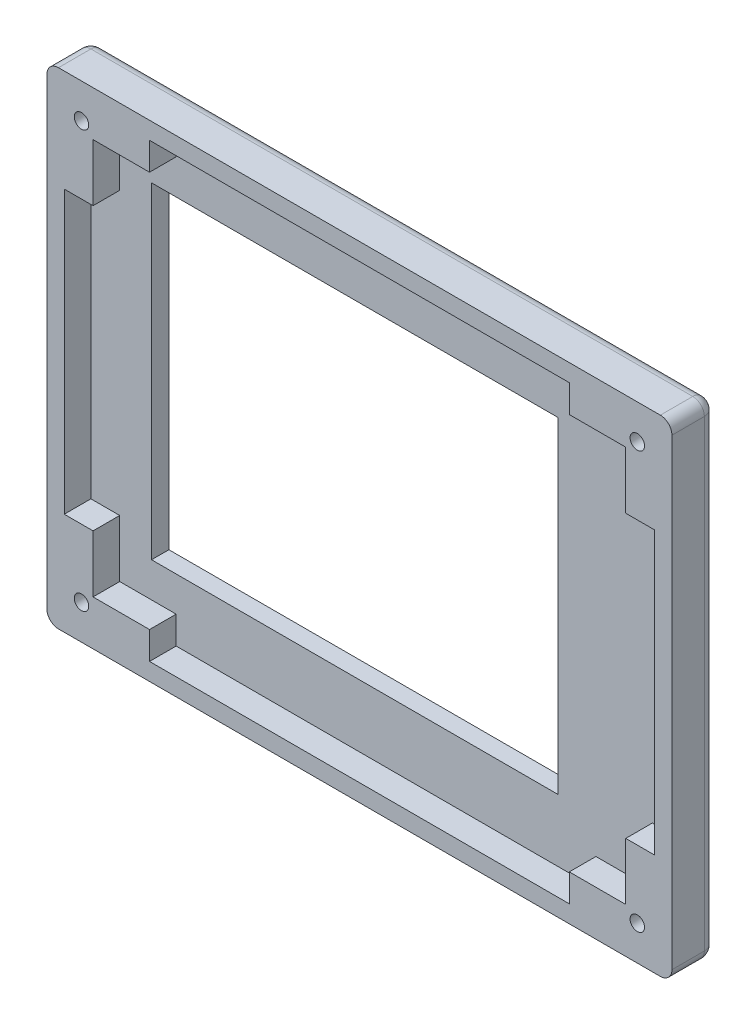
SolidWorks part; units mm, degrees
ref_plane "前视基准面" through (0, 0, 0) normal (0, 0, 1) x (1, 0, 0)
ref_plane "上视基准面" through (0, 0, 0) normal (0, 1, 0) x (1, 0, 0)
ref_plane "右视基准面" through (0, 0, 0) normal (1, 0, 0) x (0, 0, -1)
other "Configuration Table"
sketch "草图1" plane through (0, 0, 0) normal (0, 0, 1) x (1, 0, 0)
  line L32 (0.7633, 42.7757) -> (0.7633, 44.263) construction
  line L33 (0.7633, 44.263) -> (-41.2112, 44.263) construction
  line L34 (-41.2112, 44.263) -> (-41.2112, 42.7757) construction
  line L35 (-44.2239, 39.763) -> (-45.7112, 39.763) construction
  line L36 (-45.7112, 39.763) -> (-45.7112, 9.7885) construction
  line L37 (-45.7112, 9.7885) -> (-44.2239, 9.7885) construction
  line L38 (-41.2112, 6.7758) -> (-41.2112, 5.2885) construction
  line L39 (-41.2112, 5.2885) -> (0.7633, 5.2885) construction
  line L40 (0.7633, 5.2885) -> (0.7633, 6.7758) construction
  line L41 (3.776, 9.7885) -> (5.2633, 9.7885) construction
  line L42 (5.2633, 9.7885) -> (5.2633, 20.2756) construction
  line L43 (5.2633, 20.2756) -> (-0.4009, 20.283) construction
  line L44 (-0.4136, 20.2957) -> (-0.4136, 29.2557) construction
  line L45 (-0.4009, 29.2684) -> (5.2633, 29.2684) construction
  line L46 (5.2633, 29.2684) -> (5.2633, 39.763) construction
  line L47 (5.2633, 39.763) -> (3.776, 39.763) construction
  circle A1 centre (-4.0239, 32.2757) radius 1.125 construction
  arc A12 (0.7633, 42.7757) -> (3.776, 39.763) centre (3.776, 42.7757) ccw construction
  arc A13 (-44.2239, 39.763) -> (-41.2112, 42.7757) centre (-44.2239, 42.7757) ccw construction
  arc A14 (-41.2112, 6.7758) -> (-44.2239, 9.7885) centre (-44.2239, 6.7758) ccw construction
  arc A15 (3.776, 9.7885) -> (0.7633, 6.7758) centre (3.776, 6.7758) ccw construction
  arc A16 (-0.4136, 20.2957) -> (-0.4009, 20.283) centre (-0.4009, 20.2957) ccw construction
  arc A17 (-0.4009, 29.2684) -> (-0.4136, 29.2557) centre (-0.4009, 29.2557) ccw construction
sketch "草图2" plane through (0, 0, 0) normal (0, 0, 1) x (1, 0, 0)
  line L0 (0.7633, 44.263) -> (-41.2112, 44.263) construction
  line L1 (-47.2112, 45.763) -> (6.7633, 45.763)
  line L2 (-47.2112, 45.763) -> (-47.2112, 3.7885)
  line L3 (-47.2112, 3.7885) -> (6.7633, 3.7885)
  line L4 (6.7633, 45.763) -> (6.7633, 3.7885)
  line L5 (-45.7112, 39.763) -> (-45.7112, 9.7885) construction
  point P6 (-20.2239, 44.263)
  point P7 (-20.2239, 3.7885)
  point P10 (-45.7112, 24.7757)
  point P11 (-47.2112, 24.7757)
  dimension "D1" = 1.5
  dimension "D2" = 1.5
extrude "凸台-拉伸1" add sketch "草图2" along normal blind 3.8
sketch "草图3" plane through (0, 0, 3.8) normal (0, 0, 1) x (1, 0, 0)
  line L32 (0.7633, 42.7757) -> (0.7633, 44.263)
  line L33 (0.7633, 44.263) -> (-41.2112, 44.263)
  line L34 (-41.2112, 44.263) -> (-41.2112, 42.7757)
  line L35 (-44.2239, 39.763) -> (-45.7112, 39.763)
  line L36 (-45.7112, 39.763) -> (-45.7112, 9.7885)
  line L37 (-45.7112, 9.7885) -> (-44.2239, 9.7885)
  line L38 (-41.2112, 6.7758) -> (-41.2112, 5.2885)
  line L39 (-41.2112, 5.2885) -> (0.7633, 5.2885)
  line L40 (0.7633, 5.2885) -> (0.7633, 6.7758)
  line L41 (3.776, 9.7885) -> (5.2633, 9.7885)
  line L46 (5.2633, 9.7885) -> (5.2633, 39.763)
  line L47 (5.2633, 39.763) -> (3.776, 39.763)
  arc A12 (0.7633, 42.7757) -> (3.776, 39.763) centre (3.776, 42.7757) ccw
  arc A13 (-44.2239, 39.763) -> (-41.2112, 42.7757) centre (-44.2239, 42.7757) ccw
  arc A14 (-41.2112, 6.7758) -> (-44.2239, 9.7885) centre (-44.2239, 6.7758) ccw
  arc A15 (3.776, 9.7885) -> (0.7633, 6.7758) centre (3.776, 6.7758) ccw
  point P9 (5.2633, 9.4172)
extrude "切除-拉伸1" cut sketch "草图3" against normal offset from surface (2.3 mm away) 1.5 up to face at (-20.2239, 24.7757, 0)
sketch "草图6" plane through (0, 0, 0) normal (0, 0, 1) x (1, 0, 0)
  line L1 (-43.2239, 41.8757) -> (2.7761, 41.8757) construction
  line L2 (-43.2239, 41.8757) -> (-43.2239, 7.6757) construction
  line L3 (-43.2239, 7.6757) -> (2.7761, 7.6757) construction
  line L4 (2.7761, 41.8757) -> (2.7761, 7.6757) construction
  dimension "D1" = 46
  dimension "D2" = 34.2
sketch "草图4" plane through (0, 0, 3.8) normal (0, 0, 1) x (1, 0, 0)
  line L0 (6.7633, 3.7885) -> (6.7633, 45.763) construction
  line L1 (-43.2239, 41.8757) -> (2.7761, 41.8757)
  line L2 (-43.2239, 41.8757) -> (-43.2239, 7.6757)
  line L3 (-43.2239, 7.6757) -> (2.7761, 7.6757)
  line L4 (2.7761, 41.8757) -> (2.7761, 7.6757)
  line L5 (6.7633, 45.763) -> (-47.2112, 45.763) construction
  point P6 (6.7633, 24.7757)
  point P7 (2.7761, 24.7757)
  point P10 (-20.2239, 45.763)
  point P11 (-20.2239, 41.8757)
  dimension "D1" = 46
  dimension "D2" = 34.2
extrude "切除-拉伸2" cut sketch "草图4" against normal up to surface (2.3 mm away) up to face at (-20.2239, 24.7757, 1.5)
sketch "草图5" plane through (0, 0, 3.8) normal (0, 0, 1) x (1, 0, 0)
  line L0 (-20.2239, 45.763) -> (-20.2239, 3.7885) construction
  line L1 (6.7633, 45.763) -> (-47.2112, 45.763) construction
  line L2 (-47.2112, 3.7885) -> (6.7633, 3.7885) construction
  line L4 (-47.2112, 45.763) -> (-47.2112, 3.7885) construction
  line L5 (-47.2112, 24.7757) -> (6.7633, 24.7757) construction
  line L6 (6.7633, 3.7885) -> (6.7633, 45.763) construction
  circle A0 centre (-44.2239, 42.7757) radius 0.625
  circle A1 centre (3.776, 42.7757) radius 0.625
  circle A2 centre (3.776, 6.7758) radius 0.625
  circle A3 centre (-44.2239, 6.7758) radius 0.625
  dimension "D1" = 1.25
extrude "切除-拉伸3" cut sketch "草图5" against normal offset from surface (2.8 mm away) 1 up to face at (-20.2239, 24.7757, 0)
sketch "草图7" plane through (0, 0, 0) normal (0, 0, -1) x (-1, 0, 0)
  line L0 (47.2112, 45.763) -> (47.2112, 3.7885) construction
  line L1 (5.3539, 38.8707) -> (40.4739, 38.8707)
  line L2 (5.3539, 38.8707) -> (5.3539, 10.6807)
  line L3 (5.3539, 10.6807) -> (40.4739, 10.6807)
  line L4 (40.4739, 38.8707) -> (40.4739, 10.6807)
  line L5 (43.2239, 41.8757) -> (43.2239, 7.6757) construction
  point P6 (47.2112, 24.7757)
  point P7 (40.4739, 24.7757)
  dimension "D1" = 2.75
  dimension "D2" = 35.12
  dimension "D3" = 28.19
extrude "切除-拉伸4" cut sketch "草图7" against normal up to surface (1.5 mm away) up to face at (-20.2239, 24.7757, 1.5)
sketch "草图8" plane through (0, 0, 1.5) normal (0, 0, 1) x (1, 0, 0)
  line L0 (-20.2239, 45.763) -> (-20.2239, 3.7885) construction
  line L1 (-41.3487, 41.8757) -> (-38.3487, 41.8757)
  line L2 (-41.3487, 41.8757) -> (-41.3487, 44.263)
  line L3 (-41.3487, 44.263) -> (-38.3487, 44.263)
  line L4 (-38.3487, 41.8757) -> (-38.3487, 44.263)
  line L5 (6.7633, 45.763) -> (-47.2112, 45.763) construction
  line L6 (-47.2112, 3.7885) -> (6.7633, 3.7885) construction
  line L7 (0.7633, 44.263) -> (-41.2112, 44.263) construction
  line L8 (6.7633, 3.7885) -> (6.7633, 45.763) construction
  line L9 (6.7633, 24.7757) -> (-47.2112, 24.7757) construction
  line L10 (-47.2112, 45.763) -> (-47.2112, 3.7885) construction
  line L11 (-45.7112, 39.763) -> (-45.7112, 9.7885) construction
  line L12 (-43.2239, 39.9338) -> (-45.7112, 39.9338)
  line L13 (-43.2239, 39.9338) -> (-43.2239, 36.9338)
  line L14 (-43.2239, 36.9338) -> (-45.7112, 36.9338)
  line L15 (-45.7112, 39.9338) -> (-45.7112, 36.9338)
  line L16 (5.2633, 39.9338) -> (5.2633, 36.9338)
  line L17 (2.7761, 36.9338) -> (5.2633, 36.9338)
  line L18 (2.7761, 39.9338) -> (2.7761, 36.9338)
  line L19 (2.7761, 39.9338) -> (5.2633, 39.9338)
  line L20 (-2.0991, 41.8757) -> (-2.0991, 44.263)
  line L21 (0.9009, 44.263) -> (-2.0991, 44.263)
  line L22 (0.9009, 41.8757) -> (0.9009, 44.263)
  line L23 (0.9009, 41.8757) -> (-2.0991, 41.8757)
  line L28 (2.7761, 9.6177) -> (5.2633, 9.6177)
  line L29 (2.7761, 9.6177) -> (2.7761, 12.6177)
  line L30 (2.7761, 12.6177) -> (5.2633, 12.6177)
  line L31 (5.2633, 9.6177) -> (5.2633, 12.6177)
  line L32 (-45.7112, 9.6177) -> (-45.7112, 12.6177)
  line L33 (-43.2239, 12.6177) -> (-45.7112, 12.6177)
  line L34 (-43.2239, 9.6177) -> (-43.2239, 12.6177)
  line L35 (-43.2239, 9.6177) -> (-45.7112, 9.6177)
  line L40 (-41.2112, 5.2885) -> (0.7633, 5.2885) construction
  line L41 (-41.3488, 7.6757) -> (-38.3487, 7.6757)
  line L42 (-41.3488, 7.6757) -> (-41.3488, 5.2885)
  line L43 (-41.3488, 5.2885) -> (-38.3487, 5.2885)
  line L44 (-38.3487, 7.6757) -> (-38.3487, 5.2885)
  line L46 (0.9009, 7.6757) -> (-2.0991, 7.6757)
  line L47 (0.9009, 7.6757) -> (0.9009, 5.2885)
  line L48 (0.9009, 5.2885) -> (-2.0991, 5.2885)
  line L49 (-2.0991, 7.6757) -> (-2.0991, 5.2885)
  dimension "D1" = 3
  dimension "D2" = 3
extrude "凸台-拉伸2" add sketch "草图8" along normal up to surface (2.3 mm away) up to face at (-44.8489, 6.7758, 3.8)
fillet "圆角1" radius 1 8 edges at (-47.2112, 3.7885, 1.9) (-47.2112, 45.763, 1.9) (-47.2112, 24.7757, 0) (6.7633, 24.7757, 0) (6.7633, 3.7885, 1.9) (-20.2239, 3.7885, 0) (6.7633, 45.763, 1.9) (-20.2239, 45.763, 0)
